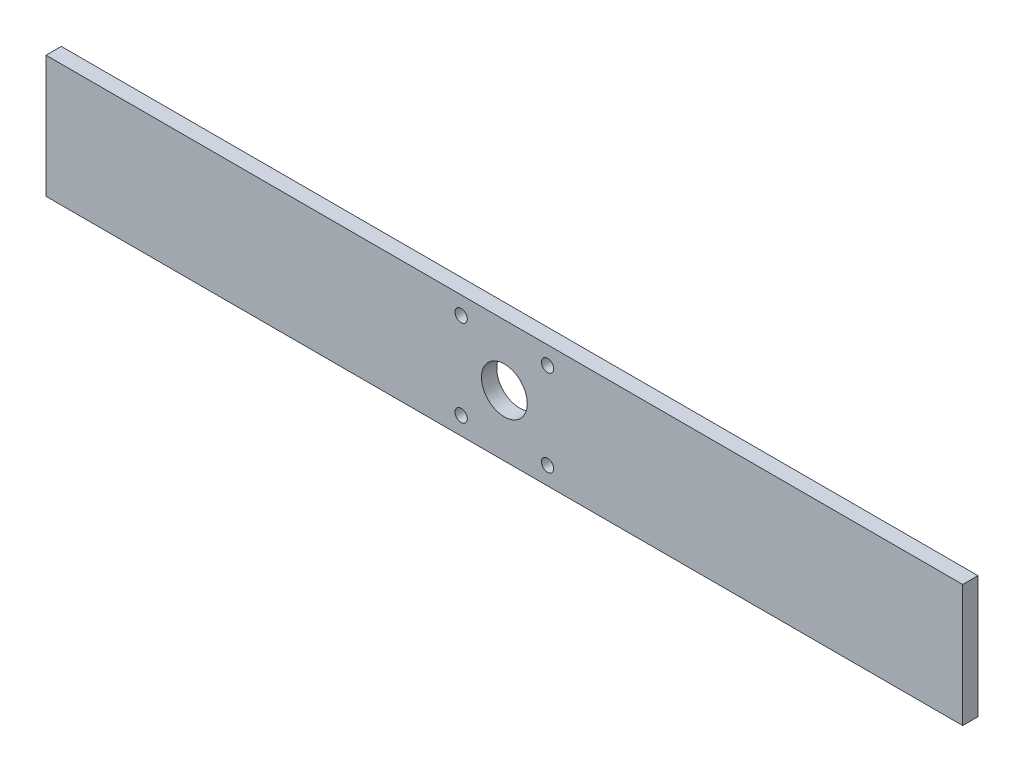
SolidWorks part; units mm, degrees
ref_plane "Front Plane" through (0, 0, 0) normal (0, 0, 1) x (1, 0, 0)
ref_plane "Top Plane" through (0, 0, 0) normal (0, 1, 0) x (1, 0, 0)
ref_plane "Right Plane" through (0, 0, 0) normal (1, 0, 0) x (0, 0, -1)
sketch "Sketch1" plane through (0, 0, 0) normal (0, 0, 1) x (1, 0, 0)
  line L1 (-190.5, -25.4) -> (190.5, -25.4)
  line L2 (-190.5, -25.4) -> (-190.5, 25.4)
  line L3 (-190.5, 25.4) -> (190.5, 25.4)
  line L4 (190.5, -25.4) -> (190.5, 25.4)
  line L5 (-190.5, -25.4) -> (190.5, 25.4) construction
  line L6 (-190.5, 25.4) -> (190.5, -25.4) construction
  point P0 (0, 0)
  dimension "D1" = 381
  dimension "D2" = 50.8
extrude "Boss-Extrude1" add sketch "Sketch1" along normal blind 6.35
sketch "Sketch2" plane through (0, 0, 6.35) normal (0, 0, 1) x (1, 0, 0)
  circle A0 centre (0, 0) radius 9.525
  dimension "D1" = 19.05
extrude "Cut-Extrude1" cut sketch "Sketch2" against normal through all
hole_wizard "#7 (0.201) Diameter Hole1" positions "Sketch4" profile "Sketch3" hole size "#7" standard "Ansi Inch" end condition through all
sketch "Sketch4" plane through (0, 0, 6.35) normal (0, 0, 1) x (1, 0, 0)
  line L0 (17.9605, 17.9605) -> (0, 0) construction
  line L1 (0, 0) -> (9.525, 0) construction
  circle A0 centre (0, 0) radius 9.525 construction
  point P0 (17.9605, 17.9605)
  dimension "D1" = 25.4
  dimension "D2" = 45
sketch "Sketch3" plane through (17.9605, 17.9605, 6.35) normal (1, 0, 0) x (0, -1, 0)
  line L0 (0, 0) -> (0, 6.35)
  line L1 (0, 6.35) -> (2.5527, 6.35)
  line L2 (2.5527, 6.35) -> (2.5527, 0)
  line L5 (2.5527, 0) -> (0, 0)
  line L11 (0, -6.35) -> (0, 107.95) construction
  dimension "Thru Hole Dia." = 5.1054
  dimension "Thru Hole Depth" = 6.35
pattern_circular "CirPattern1" count 4 over 360 about axis through (0, 0, 0) along (0, 0, 1) of "#7 (0.201) Diameter Hole1"
